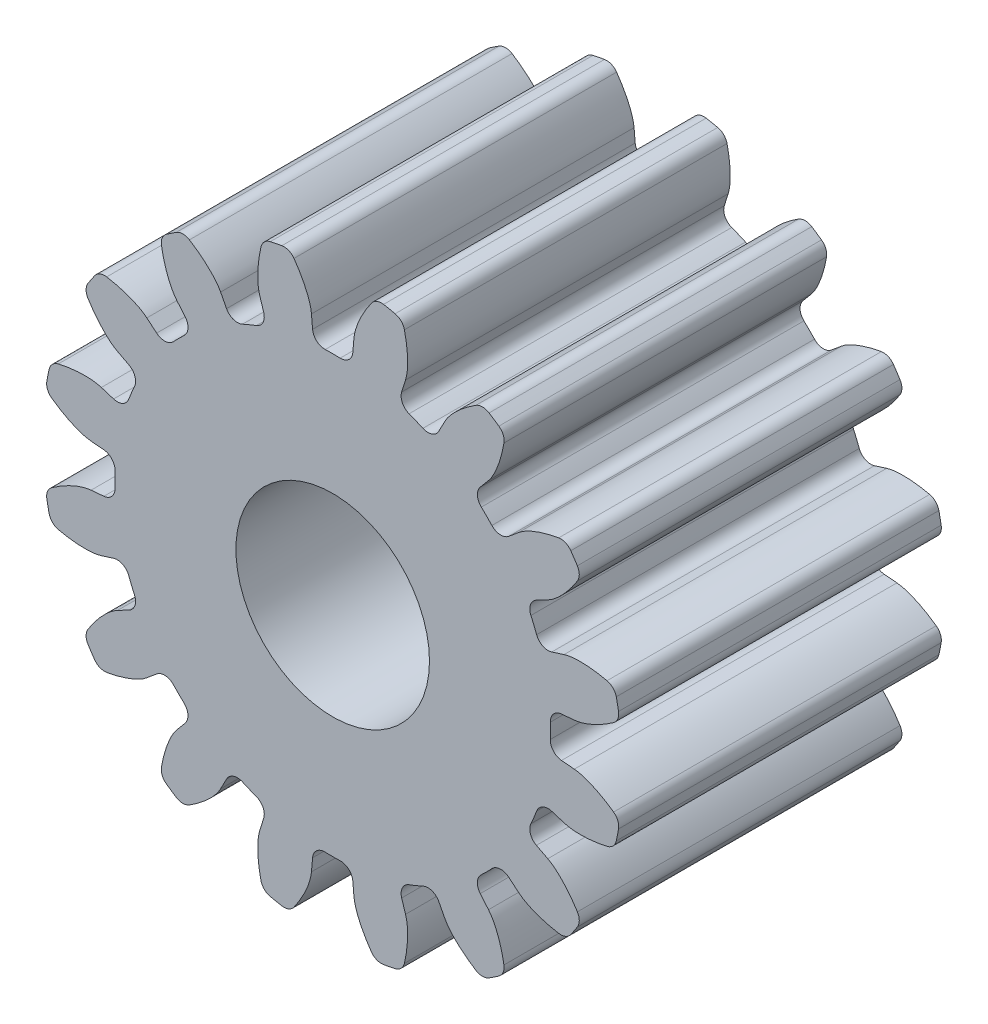
SolidWorks part; units mm, degrees
ref_plane "前视基准面" through (0, 0, 0) normal (0, 0, 1) x (1, 0, 0)
ref_plane "上视基准面" through (0, 0, 0) normal (0, 1, 0) x (1, 0, 0)
ref_plane "右视基准面" through (0, 0, 0) normal (1, 0, 0) x (0, 0, -1)
other "Configuration Table"
sketch "草图1" plane through (0, 0, 0) normal (0, 0, 1) x (1, 0, 0)
  line L0 (0, 0) -> (4, 0) construction
  line L1 (0, 0) -> (3.9807, 0.3921) construction
  line L2 (0, 0) -> (3.7443, 0.3291)
  line L3 (3.9807, 0.3921) -> (3.9807, -0.3921) construction
  line L4 (0, 0) -> (3.7443, -0.3291)
  circle A0 centre (0, 0) radius 4.5
  circle A1 centre (0, 0) radius 4 construction
  circle A2 centre (0, 0) radius 3.375
  circle A3 centre (0, 0) radius 3.7588 construction
  circle A4 centre (0, 0) radius 1.5
  spline S0 degree 4 poles (3.7443, 0.3291) (3.7729, 0.3316) (3.852, 0.3445) (3.9981, 0.3926) (4.2218, 0.5023) (4.4866, 0.6881) (4.7894, 0.9723) (5.0903, 1.3552) (5.3572, 1.8186) (5.6269, 2.4866) (5.7837, 3.1915) (5.8395, 3.939) (5.7839, 4.8292) (5.6145, 5.7064) (5.2709, 6.6864) (4.7256, 7.7028) (4.0402, 8.6299) (3.2362, 9.4556) (2.3338, 10.1718) (1.3511, 10.7732) (0.306, 11.2565) (-0.6502, 11.5751) (-1.4192, 11.7574) (-1.9866, 11.8556) (-2.3401, 11.9048) (-2.6306, 11.9368) (-2.9071, 11.9619) (-3.2112, 11.9792) (-3.4455, 11.9894) (-3.715, 11.9923) (-3.9867, 11.9914) (-4.2588, 11.9836) (-4.7357, 11.9589) (-5.1232, 11.9154) (-5.525, 11.8674) (-5.7188, 11.8311) (-5.8484, 11.8109) knots 0 0 0 0 0 0.005604 0.015718 0.02996 0.048734 0.068727 0.096889 0.125051 0.153212 0.209535 0.237696 0.271429 0.327752 0.384075 0.440398 0.496721 0.553044 0.609367 0.66569 0.722013 0.778336 0.806497 0.820578 0.834659 0.84874 0.86282 0.876901 0.890982 0.900036 0.909091 0.931818 0.954545 0.977273 1 1 1 1 1 construction
  spline S1 degree 4 poles (3.7443, 0.3291) (3.7729, 0.3316) (3.852, 0.3445) (3.9981, 0.3926) (4.2218, 0.5023) (4.4866, 0.6881) (4.7894, 0.9723) (5.0903, 1.3552) (5.3572, 1.8186) (5.6269, 2.4866) (5.7837, 3.1915) (5.8395, 3.939) (5.7839, 4.8292) (5.6145, 5.7064) (5.2709, 6.6864) (4.7256, 7.7028) (4.0402, 8.6299) (3.2362, 9.4556) (2.3338, 10.1718) (1.3511, 10.7732) (0.306, 11.2565) (-0.6502, 11.5751) (-1.4192, 11.7574) (-1.9866, 11.8556) (-2.3401, 11.9048) (-2.6306, 11.9368) (-2.9071, 11.9619) (-3.2112, 11.9792) (-3.4455, 11.9894) (-3.715, 11.9923) (-3.8743, 11.9918) (-3.9585, 11.9906) (-4.0005, 11.9898) knots 0 0 0 0 0 0.005604 0.015718 0.02996 0.048734 0.068727 0.096889 0.125051 0.153212 0.209535 0.237696 0.271429 0.327752 0.384075 0.440398 0.496721 0.553044 0.609367 0.66569 0.722013 0.778336 0.806497 0.820578 0.834659 0.84874 0.86282 0.876901 0.890982 0.900036 0.909091 0.909091 0.909091 0.909091 0.909091
  spline S2 degree 4 poles (3.7443, -0.3291) (3.7729, -0.3316) (3.852, -0.3445) (3.9981, -0.3926) (4.2218, -0.5023) (4.4866, -0.6881) (4.7894, -0.9723) (5.0903, -1.3552) (5.3572, -1.8186) (5.6269, -2.4866) (5.7837, -3.1915) (5.8395, -3.939) (5.7839, -4.8292) (5.6145, -5.7064) (5.2709, -6.6864) (4.7256, -7.7028) (4.0402, -8.6299) (3.2362, -9.4556) (2.3338, -10.1718) (1.3511, -10.7732) (0.306, -11.2565) (-0.6502, -11.5751) (-1.4192, -11.7574) (-1.9866, -11.8556) (-2.3401, -11.9048) (-2.6306, -11.9368) (-2.9071, -11.9619) (-3.2112, -11.9792) (-3.4455, -11.9894) (-3.715, -11.9923) (-3.9867, -11.9914) (-4.2588, -11.9836) (-4.7357, -11.9589) (-5.1232, -11.9154) (-5.525, -11.8674) (-5.7188, -11.8311) (-5.8484, -11.8109) knots 0 0 0 0 0 0.005604 0.015718 0.02996 0.048734 0.068727 0.096889 0.125051 0.153212 0.209535 0.237696 0.271429 0.327752 0.384075 0.440398 0.496721 0.553044 0.609367 0.66569 0.722013 0.778336 0.806497 0.820578 0.834659 0.84874 0.86282 0.876901 0.890982 0.900036 0.909091 0.931818 0.954545 0.977273 1 1 1 1 1 construction
  spline S3 degree 4 poles (3.7443, -0.3291) (3.7729, -0.3316) (3.852, -0.3445) (3.9981, -0.3926) (4.2218, -0.5023) (4.4866, -0.6881) (4.7894, -0.9723) (5.0903, -1.3552) (5.3572, -1.8186) (5.6269, -2.4866) (5.7837, -3.1915) (5.8395, -3.939) (5.7839, -4.8292) (5.6145, -5.7064) (5.2709, -6.6864) (4.7256, -7.7028) (4.0402, -8.6299) (3.2362, -9.4556) (2.3338, -10.1718) (1.3511, -10.7732) (0.306, -11.2565) (-0.6502, -11.5751) (-1.4192, -11.7574) (-1.9866, -11.8556) (-2.3401, -11.9048) (-2.6306, -11.9368) (-2.9071, -11.9619) (-3.2112, -11.9792) (-3.4455, -11.9894) (-3.715, -11.9923) (-3.8743, -11.9918) (-3.9585, -11.9906) (-4.0005, -11.9898) knots 0 0 0 0 0 0.005604 0.015718 0.02996 0.048734 0.068727 0.096889 0.125051 0.153212 0.209535 0.237696 0.271429 0.327752 0.384075 0.440398 0.496721 0.553044 0.609367 0.66569 0.722013 0.778336 0.806497 0.820578 0.834659 0.84874 0.86282 0.876901 0.890982 0.900036 0.909091 0.909091 0.909091 0.909091 0.909091
  point P15 (3.9807, 0)
  dimension "齿顶圆直径" = 9
  dimension "分度圆直径" = 8
  dimension "齿根圆直径" = 6.75
  dimension "基圆直径" = 7.5175
  dimension "内孔直径" = 3
  dimension "渐近线镜像线夹角" = 5.625
extrude "凸台-拉伸1" add sketch "草图1" along normal blind 5 contours A0 | A4
extrude "切除-拉伸1" cut sketch "草图1<3>" along normal through all contours A2 S3 A0 S1 region at (4.0116, 0, 0)
sketch "草图1<3>" plane through (0, 0, 0) normal (0, 0, 1) x (1, 0, 0) same geometry as "草图1"
fillet "圆角1" radius 0.19 4 edges at (4.4495, 0.6722, 2.5) (4.4495, -0.6722, 2.5) (3.362, 0.2955, 2.5) (3.362, -0.2955, 2.5)
pattern_circular "阵列(圆周)1" count 16 every 22.5 about axis through (0, 0, 5) along (0, 0, 1) of "切除-拉伸1", "圆角1"
equation "\"m\" = 0.5'模数"
equation "\"z\" = 16'齿数"
equation "\"a\"= 20度'压力角"
equation "\"d\"= \"m\" * \"z\"'分度圆直径"
equation "\"da\"= ( \"z\" + 2 ) * \"m\"'齿顶圆直径"
equation "\"df\"= ( \"z\" - 2.5 ) * \"m\"'齿根圆直径"
equation "\"s\"= 0.5 * PI * \"m\"'分度圆齿厚"
equation "\"r\"= 0.38 * \"m\"'齿根圆角"
equation "\"B\"= 0.3 * \"d\"'齿厚"
equation "\"db\"= \"m\" * \"z\" * cos ( \"a\" )'基圆直径"
equation "\"rb\"= \"db\" / 2'基圆半径"
equation "\"齿顶圆直径@草图1\"= \"da\""
equation "\"分度圆直径@草图1\"= \"d\""
equation "\"齿根圆直径@草图1\"= \"df\""
equation "\"基圆直径@草图1\"= \"db\""
equation "\"渐近线镜像线夹角@草图1\"= 360 / 4 / \"z\""
equation "\"h\"= 5'齿轮厚度"
equation "\"ir\"= 3'内孔直径"
equation "\"内孔直径@草图1\"= \"ir\""
equation "\"齿轮厚@凸台-拉伸1\"= \"h\""
equation "\"齿轮夹角@阵列(圆周)1\"= 360 / \"z\""
equation "\"齿数@阵列(圆周)1\"= \"z\""
equation "\"D1@圆角1\"=\"m\"*0.38"
